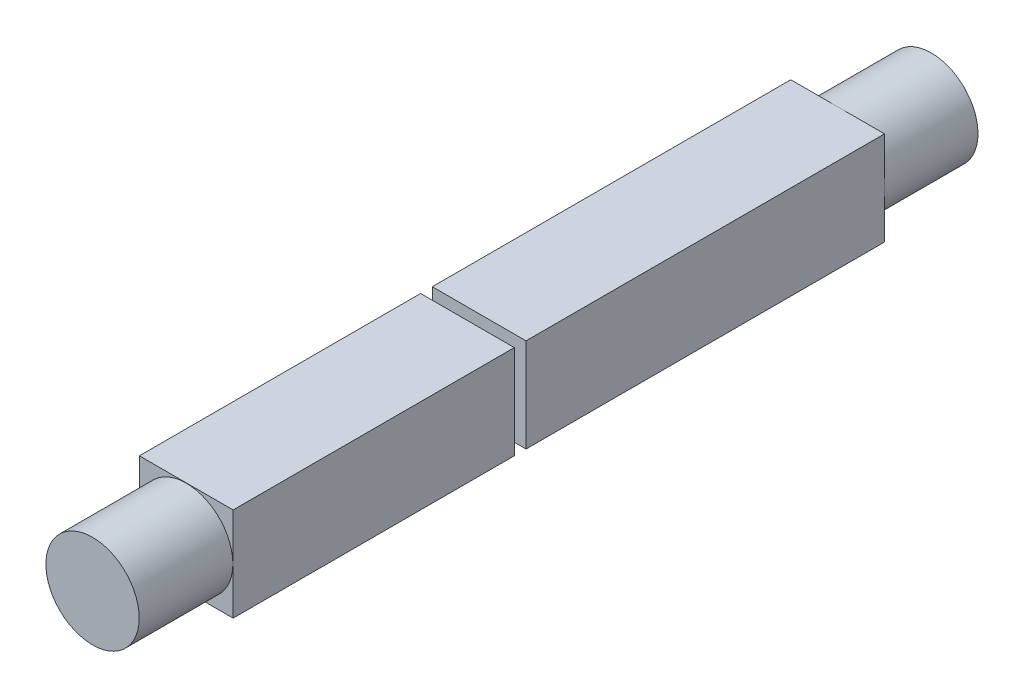
SolidWorks part; units mm, degrees
ref_plane "Front Plane" through (0, 0, 0) normal (0, 0, 1) x (1, 0, 0)
ref_plane "Top Plane" through (0, 0, 0) normal (0, 1, 0) x (1, 0, 0)
ref_plane "Right Plane" through (0, 0, 0) normal (1, 0, 0) x (0, 0, -1)
sketch "Sketch1" plane through (0, 0, 0) normal (0, 0, 1) x (1, 0, 0)
  line L1 (2, -2) -> (-2, -2)
  line L2 (2, -2) -> (2, 2)
  line L3 (2, 2) -> (-2, 2)
  line L4 (-2, -2) -> (-2, 2)
  line L5 (2, -2) -> (-2, 2) construction
  line L6 (2, 2) -> (-2, -2) construction
  dimension "D2" = 4
extrude "Boss-Extrude1" add sketch "Sketch1" along normal mid plane 27.8
sketch "Sketch2" plane through (0, 0, 13.9) normal (0, 0, 1) x (1, 0, 0)
  circle A0 centre (0, 0) radius 1.99
  dimension "D1" = 3.98
extrude "Boss-Extrude2" add sketch "Sketch2" along normal blind 4
mirror "Mirror2" about plane through (0, 0, 0) normal (0, 0, 1) of "Boss-Extrude2"
sketch "Sketch3" plane through (0, 2, 0) normal (0, 1, 0) x (1, 0, 0)
  line L0 (-2, -13.9) -> (-2, 13.9) construction
  line L1 (-2, -1.9) -> (2, -1.9)
  line L2 (-2, -1.9) -> (-2, -1.4)
  line L3 (-2, -1.4) -> (2, -1.4)
  line L4 (2, -1.9) -> (2, -1.4)
  line L5 (2, -13.9) -> (2, 13.9) construction
  line L7 (2, -13.9) -> (-2, -13.9) construction
  point P10 (-2, -3.5397)
  dimension "D1" = 0.5
  dimension "D2" = 12
extrude "Cut-Extrude1" cut sketch "Sketch3" against normal up to next
